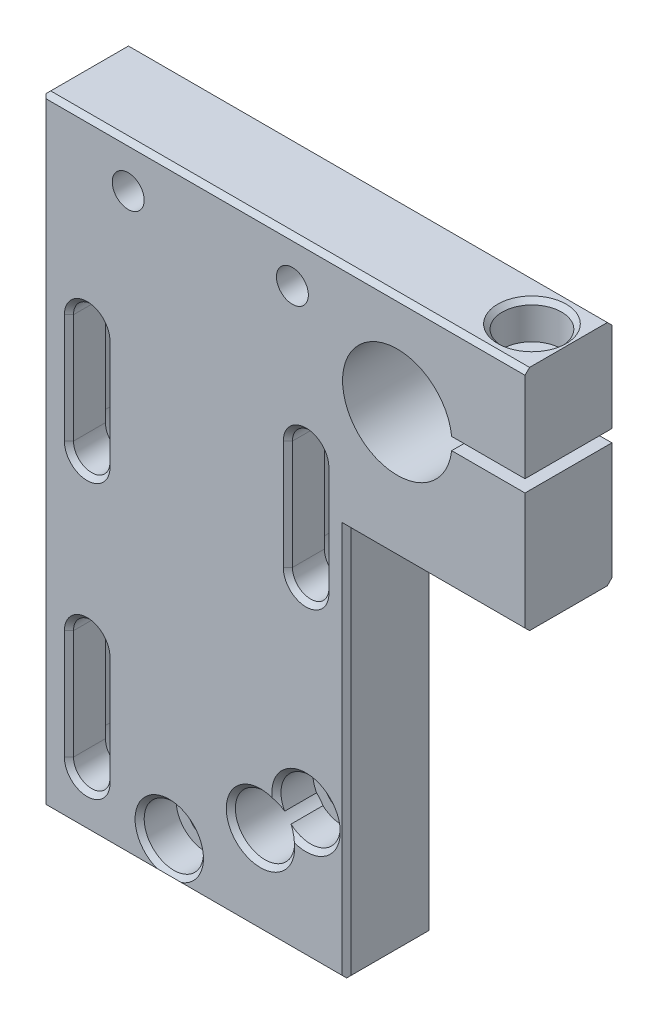
SolidWorks part; units mm, degrees
ref_plane "Front Plane" through (0, 0, 0) normal (0, 0, 1) x (1, 0, 0)
ref_plane "Top Plane" through (0, 0, 0) normal (0, 1, 0) x (1, 0, 0)
ref_plane "Right Plane" through (0, 0, 0) normal (1, 0, 0) x (0, 0, -1)
sketch "Sketch1" plane through (0, 0, 0) normal (0, 0, 1) x (1, 0, 0)
  line L0 (0, 0) -> (24.45, 0)
  line L1 (30, -16) -> (30, 43) construction
  line L3 (24.45, 43) -> (24.45, 0)
  line L4 (24.45, 0) -> (24.6859, 0.0472)
  line L6 (24.45, 43) -> (58.5, 43)
  line L8 (0, 68) -> (58.5, 68)
  line L9 (58.5, 43) -> (58.5, 68)
  line L10 (0, 0) -> (-9, 0)
  line L12 (0, 68) -> (-9, 68)
  line L13 (-9, 0) -> (-9, 68)
  circle A0 centre (5, 4) radius 2
  circle A1 centre (20, 14) radius 2
  circle A2 centre (15, 10) radius 3.25
  circle A3 centre (5, 4) radius 3.25
  circle A4 centre (30, -16) radius 6.55
  circle A5 centre (20, 14) radius 3.25
  dimension "D3" = 4
  dimension "D7" = 4
  dimension "D10" = 6.5
  dimension "D13" = 13.1
  dimension "D19" = 6.5
  dimension "D20" = 6.5
  dimension "D1" = 24.45
  dimension "D2" = 4
  dimension "D4" = 5
  dimension "D5" = 20
  dimension "D6" = 14
  dimension "D8" = 10
  dimension "D9" = 15
  dimension "D11" = 30
  dimension "D12" = 16
  dimension "D14" = 43
  dimension "D15" = 58.5
  dimension "D16" = 67.5
  dimension "D17" = 9
  dimension "D18" = 68
extrude "Boss-Extrude1" add sketch "Sketch1" along normal blind 9.525 contours L13 L10 L0 L3 L6 L9 L8 L12 A2 A1 A0 region at (17.0339, 40.8583, 0)
extrude "Boss-Extrude3" add sketch "Sketch1<4>" along normal blind 5.525 contours A2 A5 A1 | A3 A0 region at (17.6096, 12.0877, 0) region at (1.8419, 4, 0)
sketch "Sketch1<4>" plane through (0, 0, 0) normal (0, 0, 1) x (1, 0, 0) same geometry as "Sketch1"
sketch "Sketch3" plane through (0, 0, 9.525) normal (0, 0, 1) x (1, 0, 0)
  line L0 (-2, 18) -> (-2, 6)
  line L1 (-9, 0) -> (-9, 68) construction
  line L2 (24.45, 0) -> (-9, 0) construction
  line L3 (-6, 18) -> (-6, 6)
  line L4 (-6, 48) -> (-6, 36)
  line L5 (-2, 48) -> (-2, 36)
  line L6 (18, 48) -> (18, 36)
  line L7 (22, 48) -> (22, 36)
  arc A0 (-2, 18) -> (-6, 18) centre (-4, 18) ccw
  arc A1 (-2, 48) -> (-6, 48) centre (-4, 48) ccw
  arc A2 (22, 48) -> (18, 48) centre (20, 48) ccw
  arc A7 (-6, 6) -> (-2, 6) centre (-4, 6) ccw
  arc A8 (-6, 36) -> (-2, 36) centre (-4, 36) ccw
  arc A11 (18, 36) -> (22, 36) centre (20, 36) ccw
  dimension "D3" = 4
  dimension "D4" = 4
  dimension "D5" = 4
  dimension "D6" = 5
  dimension "D7" = 6
  dimension "D8" = 12
  dimension "D11" = 4
  dimension "D12" = 4
  dimension "D13" = 4
  dimension "D1" = 24
  dimension "D2" = 30
  dimension "D9" = 12
  dimension "D10" = 12
  dimension "D14" = 12
  dimension "D15" = 12
  dimension "D16" = 12
  dimension "D17" = 12
  dimension "D18" = 12
  dimension "D19" = 12
extrude "Cut-Extrude1" cut sketch "Sketch3" against normal through all
sketch "Sketch4" plane through (0, 0, 0) normal (0, 0, -1) x (-1, 0, 0)
  line L4 (-16.75, 36) -> (-16.75, 48)
  line L5 (-23.25, 48) -> (-23.25, 36)
  line L8 (0.75, 48) -> (0.75, 36)
  line L9 (7.25, 36) -> (7.25, 48)
  line L12 (7.25, 6) -> (7.25, 18)
  line L13 (0.75, 17.9953) -> (0.75, 5.9953)
  arc A0 (2, 6) -> (6, 6) centre (4, 6) ccw construction
  arc A1 (6, 18) -> (2, 18) centre (4, 18) ccw construction
  arc A2 (2, 36) -> (6, 36) centre (4, 36) ccw construction
  arc A3 (6, 48) -> (2, 48) centre (4, 48) ccw construction
  arc A4 (-23.25, 36) -> (-16.75, 36) centre (-20, 36) ccw
  arc A5 (-16.75, 48) -> (-23.25, 48) centre (-20, 48) ccw
  arc A6 (-22, 36) -> (-18, 36) centre (-20, 36) ccw construction
  arc A7 (-18, 48) -> (-22, 48) centre (-20, 48) ccw construction
  arc A8 (0.75, 36) -> (7.25, 36) centre (4, 36) ccw
  arc A9 (7.25, 48) -> (0.75, 48) centre (4, 48) ccw
  arc A12 (0.75, 5.9953) -> (7.25, 6) centre (4, 6) ccw
  arc A13 (7.25, 18) -> (0.75, 17.9953) centre (4, 18) ccw
  dimension "D4" = 3.25
  dimension "D1" = 3.25
  dimension "D6" = 3.25
  dimension "D7" = 3.25
  dimension "D11" = 3.25
  dimension "D12" = 3.25
  dimension "D2" = 12
  dimension "D3" = 12
  dimension "D5" = 6.5
  dimension "D8" = 12
  dimension "D9" = 12
  dimension "D10" = 6.5
  dimension "D13" = 12
  dimension "D14" = 12
  dimension "D15" = 6.5
extrude "Cut-Extrude2" cut sketch "Sketch4" against normal blind 5.525
chamfer "Chamfer1" distance 0.5 angle 45 1 edges at (-9, 68, 4.7625)
chamfer "Chamfer2" distance 0.5 angle 45 4 edges at (-9, 0, 4.7625) (24.45, 0, 4.7625) (58.5, 43, 4.7625) (58.5, 68, 4.7625)
chamfer "Chamfer3" distance 0.5 angle 45 12 edges at (24.75, 68, 0) (58.5, 55.5, 0) (41.225, 43, 0) (24.45, 21.75, 0) (24.75, 68, 9.525) (58.5, 55.5, 9.525) (41.225, 43, 9.525) (24.45, 21.75, 9.525) (7.725, 0, 0) (7.725, 0, 9.525) (-9, 34, 0) (-9, 34, 9.525)
chamfer "Chamfer4" distance 0.5 angle 45 15 edges at (20, 34, 9.525) (22, 42, 9.525) (20, 50, 9.525) (18, 42, 9.525) (-4, 34, 9.525) (-2, 42, 9.525) (-4, 50, 9.525) (-6, 42, 9.525) (-6, 12, 9.525) (-4, 4, 9.525) (-2, 12, 9.525) (-4, 20, 9.525) (8.25, 4, 9.525) (22.5378, 16.0303, 9.525) (12.4622, 7.9697, 9.525)
sketch "Sketch6" plane through (0, 0, 9.525) normal (0, 0, 1) x (1, 0, 0)
  line L0 (0, 68) -> (58.5, 68) construction
  line L1 (22.5, 48) -> (22.5, 36) construction
  line L2 (30, 57.675) -> (50, 57.675)
  line L3 (30, 57.675) -> (30, 56.325)
  line L4 (30, 56.325) -> (50, 56.325)
  line L5 (50, 57.675) -> (50, 56.325)
  line L6 (79, 1) -> (29, 1)
  line L7 (79, 1) -> (79, 51)
  line L8 (79, 51) -> (29, 51)
  line L9 (29, 1) -> (29, 51)
  line L10 (-9, 0) -> (-9, 68) construction
  circle A0 centre (30, 57) radius 6
  dimension "D1" = 12
  dimension "D2" = 73
  dimension "D3" = 1.35
  dimension "D4" = 0.675
  dimension "D5" = 20
  dimension "D6" = 17
  dimension "D7" = 38
  dimension "D8" = 50
  dimension "D9" = 50
sketch "Sketch7" plane through (0, 0, 9.525) normal (0, 0, 1) x (1, 0, 0)
  line L0 (0, 68) -> (58.5, 68) construction
  line L1 (58.5, 43) -> (44, 43)
  line L2 (58.5, 43) -> (58.5, 68)
  line L3 (58.5, 68) -> (44, 68)
  line L4 (44, 43) -> (44, 68)
  dimension "D1" = 14
extrude "Cut-Extrude4" cut sketch "Sketch7" against normal through all
extrude "Cut-Extrude5" cut sketch "Sketch6" against normal through all contours L2 A0 L4 L3 | L4 A0 L2 L3 | A0 L4 L5 L2 region at (29.7696, 57, 9.525) region at (32.9937, 57, 9.525) region at (42.9937, 57, 9.525)
sketch "Sketch9" plane through (0, 0, 9.525) normal (0, 0, 1) x (1, 0, 0)
  line L0 (-8.5, 68) -> (44, 68) construction
  line L1 (-9, 0.5) -> (-9, 67.5) construction
  circle A0 centre (0.5, 63.2375) radius 1.75
  circle A1 centre (18.5, 63.2375) radius 1.75
  circle A2 centre (0.5, 63.2375) radius 3.25
  circle A3 centre (18.5, 63.2375) radius 3.25
  dimension "D1" = 3.5
  dimension "D2" = 3.5
  dimension "D3" = 6.5
  dimension "D6" = 6.5
  dimension "D4" = 4.7625
  dimension "D5" = 4.7625
  dimension "D7" = 9.5
  dimension "D8" = 18
sketch "Sketch10" plane through (0, 0, 0) normal (0, 0, -1) x (-1, 0, 0)
  circle A0 centre (-18.5, 63.2375) radius 1.75 construction
  circle A1 centre (-18.5, 63.2375) radius 3.25 construction
  circle A2 centre (-0.5, 63.2375) radius 1.75 construction
  circle A3 centre (-0.5, 63.2375) radius 3.25 construction
  circle A4 centre (-18.5, 63.2375) radius 1.75
  circle A5 centre (-18.5, 63.2375) radius 3.25
  circle A6 centre (-0.5, 63.2375) radius 1.75
  circle A7 centre (-0.5, 63.2375) radius 3.25
extrude "Cut-Extrude6" cut sketch "Sketch10" against normal blind 4
extrude "Cut-Extrude7" cut sketch "Sketch9" against normal through all contours A0 | A1 region at (0.5, 63.2375, 9.525) region at (18.5, 63.2375, 9.525)
chamfer "Chamfer5" distance 0.5 angle 45 2 edges at (-2.75, 63.2375, 0) (15.25, 63.2375, 0)
sketch "Sketch12" plane through (0, 68, 0) normal (0, 1, 0) x (1, 0, 0)
  line L0 (44, -0.5) -> (44, -9.025) construction
  line L1 (-8.5, 0) -> (44, 0) construction
  circle A0 centre (40, -4.7625) radius 1.75
  circle A1 centre (40, -4.7625) radius 3.25
  dimension "D3" = 3.5
  dimension "D4" = 6.5
  dimension "D1" = 4
  dimension "D2" = 4.7625
extrude "Cut-Extrude8" cut sketch "Sketch12" against normal up to surface (10.325 mm away) contours A0 region at (40, 68, 4.7625) up to face at (39.981, 57.675, 4.7625)
sketch "Sketch13" plane through (0, 43, 0) normal (0, -1, 0) x (1, 0, 0)
  line L0 (44, 0) -> (23.95, 0) construction
  line L1 (44, 0.5) -> (44, 9.025) construction
  circle A0 centre (40, 4.7625) radius 1.2195
  dimension "D1" = 2.439
  dimension "D2" = 4.7625
  dimension "D3" = 4
extrude "Cut-Extrude9" cut sketch "Sketch13" against normal up to surface (13.325 mm away) up to face at (39.981, 56.325, 4.7625)
extrude "Cut-Extrude10" cut sketch "Sketch12<3>" against normal blind 4
sketch "Sketch12<3>" plane through (0, 68, 0) normal (0, 1, 0) x (1, 0, 0) same geometry as "Sketch12"
chamfer "Chamfer6" distance 0.5 angle 45 1 edges at (36.75, 68, 4.7625)
